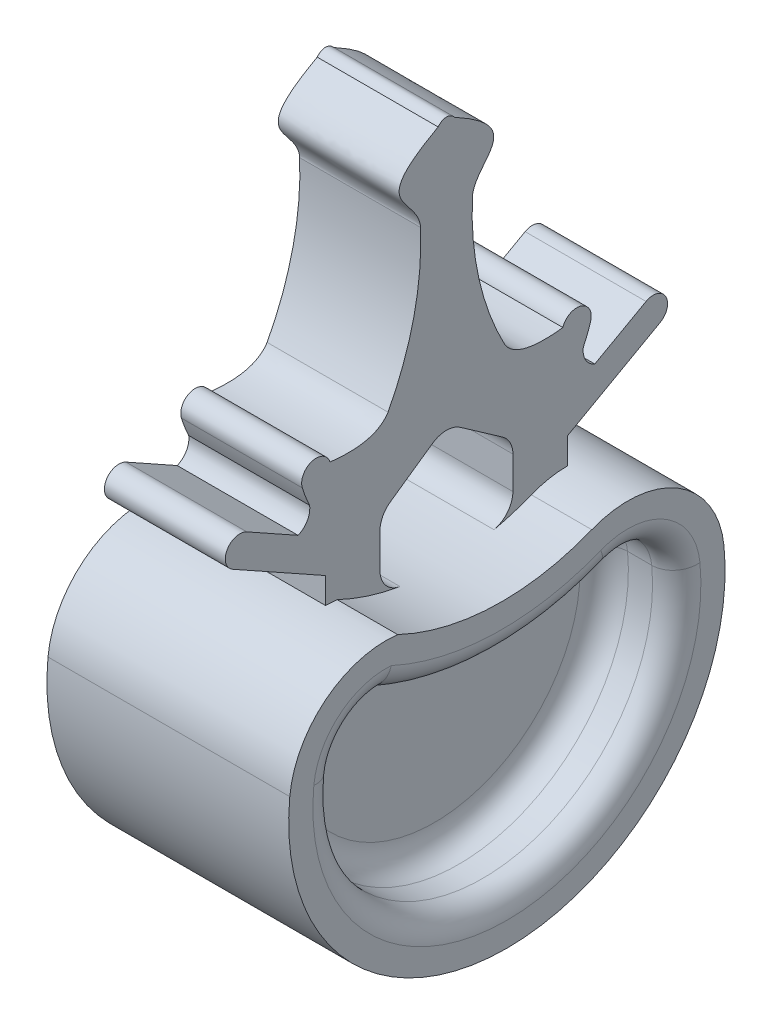
SolidWorks part; units mm, degrees
ref_plane "前视基准面" through (0, 0, 0) normal (0, 0, 1) x (1, 0, 0)
ref_plane "上视基准面" through (0, 0, 0) normal (0, 1, 0) x (1, 0, 0)
ref_plane "右视基准面" through (0, 0, 0) normal (1, 0, 0) x (0, 0, -1)
other "Configuration Table"
sketch "Sketch3" plane through (0, 0, 0) normal (1, 0, 0) x (0, 0, -1)
  line L0 (0, 0) -> (-5, 0) construction
  line L1 (0, 0) -> (5, 0) construction
  arc A0 (-5, 0) -> (5, 0) centre (0, -0.5) ccw construction
  arc A1 (-8.9801, 0.398) -> (8.9801, 0.398) centre (0, -0.5) ccw
  arc A4 (8.9801, 0.398) -> (3.5117, 3.7128) centre (5, 0) ccw
  arc A5 (-4.5181, 3.9709) -> (3.5117, 3.7128) centre (-0.209, 12.9948) ccw
  arc A6 (-4.5181, 3.9709) -> (-8.9801, 0.398) centre (-5, 0) ccw
  point P5 (0, -5.5249)
  point P8 (-0.5302, 3)
  dimension "D4" = 4
  dimension "D5" = 10
  dimension "D3" = 4
  dimension "D7" = 9.0249
  dimension "D1" = 5
  dimension "D2" = 5
  dimension "D6" = 3
  dimension "D8" = 0.5
extrude "Boss-Extrude2" add sketch "Sketch3" along normal blind 10
sketch "Sketch4" plane through (10, 0, 0) normal (1, 0, 0) x (0, 0, -1)
  arc A8 (-5.0165, 1.9999) -> (-6.9901, 0.199) centre (-5, 0) ccw
  arc A9 (-6.9901, 0.199) -> (6.9901, 0.199) centre (0, -0.5) ccw
  arc A10 (6.9901, 0.199) -> (4.2559, 1.8564) centre (5, 0) ccw
  arc A11 (-5.0165, 1.9999) -> (4.2559, 1.8564) centre (-0.209, 12.9948) ccw
  arc A12 (-5.0165, 1.9999) -> (-6.9901, 0.199) centre (-5, 0) ccw
  arc A13 (-6.9901, 0.199) -> (6.9901, 0.199) centre (0, -0.5) ccw
  arc A14 (6.9901, 0.199) -> (4.2559, 1.8564) centre (5, 0) ccw
  arc A15 (-5.0165, 1.9999) -> (4.2559, 1.8564) centre (-0.209, 12.9948) ccw
  dimension "D1" = 2
extrude "Cut-Extrude1" cut sketch "Sketch4" against normal blind 3
ref_plane "Plane1" through (5, 0, 0) normal (1, 0, 0) x (0, 0, -1)
sketch "Sketch5" plane through (5, 0, 0) normal (1, 0, 0) x (0, 0, -1)
  line L0 (0, 0) -> (0, 8) construction
  line L1 (0, 8) -> (2.7485, 6.0755)
  line L2 (2.7485, 6.0755) -> (2.7485, 3.3062)
  line L3 (0, 8) -> (0, 13) construction
  line L4 (0, 10.5) -> (4.9985, 7)
  line L5 (4.9985, 7) -> (4.9985, 4)
  line L6 (-4.9985, 7) -> (-4.9985, 4)
  line L7 (-2.7485, 6.0755) -> (-2.7485, 3.3062)
  line L8 (0, 8) -> (-2.7485, 6.0755)
  line L9 (0, 10.5) -> (-4.9985, 7)
  line L10 (0, 13) -> (0, 18) construction
  line L11 (1.3449, 9.5583) -> (0.5651, 18.4709)
  line L12 (-1.3449, 9.5583) -> (-0.5651, 18.4709)
  arc A0 (8.9801, 0.398) -> (3.5117, 3.7128) centre (5, 0) ccw construction
  arc A9 (-4.5181, 3.9709) -> (-8.9801, 0.398) centre (-5, 0) ccw
  arc A10 (-8.9801, 0.398) -> (8.9801, 0.398) centre (0, -0.5) ccw
  arc A11 (8.9801, 0.398) -> (3.5117, 3.7128) centre (5, 0) ccw
  arc A12 (-4.5181, 3.9709) -> (3.5117, 3.7128) centre (-0.209, 12.9948) ccw
  arc A13 (-4.5181, 3.9709) -> (-8.9801, 0.398) centre (-5, 0) ccw
  arc A14 (-8.9801, 0.398) -> (8.9801, 0.398) centre (0, -0.5) ccw
  arc A15 (8.9801, 0.398) -> (3.5117, 3.7128) centre (5, 0) ccw
  arc A16 (-4.5181, 3.9709) -> (3.5117, 3.7128) centre (-0.209, 12.9948) ccw
  ellipse E0 centre (0, 18) end of major axis (0, 19) minor radius 0.6
  dimension "D1" = 8
  dimension "D2" = 5
  dimension "D3" = 2.25
  dimension "D4" = 125
  dimension "D5" = 3
  dimension "D6" = 5
  dimension "D7" = 1.2
  dimension "D8" = 2
  dimension "D9" = 50
  dimension "D10" = 0
extrude "Boss-Extrude3" add sketch "Sketch5" along normal mid plane 5 contours A15 L5 L4 L9 L6 A13 L7 L8 L1 L2 | E0 L12 L9 L4 L11 | E0 L9 region at (5, 7.1385, 1.4448) region at (5, 13.2604, 0) region at (5, 18, 0)
sketch "Sketch7" plane through (5, 0, 0) normal (1, 0, 0) x (0, 0, -1)
  line L0 (0, 19) -> (0, 0) construction
  line L1 (2.7485, 6.0755) -> (4.9985, 7) construction
  line L2 (4.9985, 7) -> (3.8735, 6.5377) construction
  line L3 (4.1823, 5.3066) -> (8.5466, 7.7435) construction
  line L4 (3.8897, 5.8305) -> (8.2541, 8.2674)
  line L5 (4.4748, 4.7828) -> (8.8391, 7.2197)
  line L6 (5, 4) -> (5, 5.076)
  line L7 (-5, 4) -> (-5, 5.076)
  line L8 (-4.1823, 5.3066) -> (-8.5466, 7.7435) construction
  line L9 (-3.8897, 5.8305) -> (-8.2541, 8.2674)
  line L10 (-4.4748, 4.7828) -> (-8.8391, 7.2197)
  line L74 (-5, 4) -> (-4.9985, 7)
  line L75 (-4.9985, 7) -> (-1.3449, 9.5583)
  line L76 (-1.3449, 9.5583) -> (-0.5937, 18.1443)
  line L77 (-0.5937, 18.1443) -> (0.5937, 18.1443)
  line L78 (0.5937, 18.1443) -> (1.3449, 9.5583)
  line L79 (1.3449, 9.5583) -> (4.9985, 7)
  line L80 (4.9985, 7) -> (5, 4)
  line L81 (4.9985, 7) -> (5, 4)
  line L82 (-5, 4) -> (0, 0)
  line L83 (0, 0) -> (5, 4)
  line L84 (-5, 4) -> (5, 4)
  arc A0 (3.8735, 6.5377) -> (5.389, 8.8743) centre (0.5038, 10.383) ccw construction
  arc A1 (4.269, 6.0865) -> (5.9623, 8.6972) centre (0.5038, 10.383) ccw
  arc A2 (3.4781, 6.989) -> (4.8157, 9.0513) centre (0.5038, 10.383) ccw
  arc A3 (3.4781, 6.989) -> (4.269, 6.0865) centre (3.8735, 6.5377) ccw
  arc A4 (5.9623, 8.6972) -> (4.8157, 9.0513) centre (5.389, 8.8743) ccw
  arc A5 (1.0768, 15.6644) -> (2.4164, 9.6362) centre (12.6356, 15.07) ccw
  arc A6 (5.66, 7.9233) -> (6.1364, 7.0849) centre (6.4354, 7.8094) ccw
  arc A7 (3.8897, 5.8305) -> (4.4748, 4.7828) centre (4.1823, 5.3066) ccw
  arc A8 (8.8391, 7.2197) -> (8.2541, 8.2674) centre (8.5466, 7.7435) ccw
  arc A9 (8.9801, 0.398) -> (3.5117, 3.7128) centre (5, 0) ccw construction
  arc A10 (-3.8897, 5.8305) -> (-4.4748, 4.7828) centre (-4.1823, 5.3066) cw
  arc A11 (-8.8391, 7.2197) -> (-8.2541, 8.2674) centre (-8.5466, 7.7435) cw
  arc A12 (-5.66, 7.9233) -> (-6.1364, 7.0849) centre (-6.4354, 7.8094) cw
  arc A13 (-3.8735, 6.5377) -> (-5.389, 8.8743) centre (-0.5038, 10.383) cw construction
  arc A14 (-4.269, 6.0865) -> (-5.9623, 8.6972) centre (-0.5038, 10.383) cw
  arc A15 (-3.4781, 6.989) -> (-4.8157, 9.0513) centre (-0.5038, 10.383) cw
  arc A16 (-3.4781, 6.989) -> (-4.269, 6.0865) centre (-3.8735, 6.5377) cw
  arc A17 (-5.9623, 8.6972) -> (-4.8157, 9.0513) centre (-5.389, 8.8743) cw
  arc A18 (-1.0768, 15.6644) -> (-2.4164, 9.6362) centre (-12.6356, 15.07) cw
  ellipse E0 centre (0, 18) end of major axis (0, 19) minor radius 0.6 (0.5937, 18.1443) -> (-0.5937, 18.1443) ccw construction
  spline S0 degree 3 poles (0, 19) (3.4903, 17.2101) (1.2443, 16.8956) (1.0686, 15.6113) (1.073, 15.5843) knots 0 0 0 0 0.318084 0.324852 0.324852 0.324852 0.324852
  spline S1 degree 2 poles (2.4164, 9.6362) (2.9382, 8.8227) (4.8157, 9.0513) knots 0.827735 0.827735 0.827735 1 1 1
  spline S2 degree 2 poles (-2.4164, 9.6362) (-2.9382, 8.8227) (-4.8157, 9.0513) knots 0.827735 0.827735 0.827735 1 1 1
  spline S3 degree 3 poles (0, 19) (-3.4903, 17.2101) (-1.2443, 16.8956) (-1.0686, 15.6113) (-1.073, 15.5843) knots 0 0 0 0 0.318084 0.324852 0.324852 0.324852 0.324852
  point P17 (4.7934, 7.6008)
  point P28 (6.3644, 6.5251)
  point P49 (-6.3644, 6.5251)
  point P60 (-4.7934, 7.6008)
  point P78 (5.389, 8.8743)
  dimension "D1" = 0.6
  dimension "D2" = 0.6
  dimension "D3" = 0
extrude "Boss-Extrude4" add sketch "Sketch7" along normal mid plane 5 contours A17 A14 L74 L75 A15 | L74 A14 A12 L9 | A11 L10 L74 L9 | S0 S3 A18 S2 A15 L75 L76 L77 L78 L79 A2 S1 A5 | A1 A4 A2 L79 L80 | A6 A1 L81 L4 | L5 A8 L4 L80 region at (5, 6.8541, -6.9839) region at (5, 7.07, -5.4863) region at (5, 8.2716, -5.135) region at (5, 8.381, -4.3814) region at (5, 6.8541, 6.9839) region at (5, 7.07, 5.4863) region at (5, 8.2716, 5.135)
fillet "Fillet2" radius 1 5 edges at (5, 3.3227, 2.7485) (5, 3.4422, -2.7485) (5, 6.0755, -2.7485) (5, 8, 0) (5, 6.0755, 2.7485)
sketch "Sketch10" plane through (0, 0, 0) normal (-1, 0, 0) x (0, 0, 1)
  arc A8 (6.9901, 0.199) -> (5.0165, 1.9999) centre (5, 0) ccw
  arc A9 (-4.2559, 1.8564) -> (5.0165, 1.9999) centre (0.209, 12.9948) ccw
  arc A10 (-4.2559, 1.8564) -> (-6.9901, 0.199) centre (-5, 0) ccw
  arc A11 (-6.9901, 0.199) -> (6.9901, 0.199) centre (0, -0.5) ccw
  arc A12 (6.9901, 0.199) -> (5.0165, 1.9999) centre (5, 0) ccw
  arc A13 (-4.2559, 1.8564) -> (5.0165, 1.9999) centre (0.209, 12.9948) ccw
  arc A14 (-4.2559, 1.8564) -> (-6.9901, 0.199) centre (-5, 0) ccw
  arc A15 (-6.9901, 0.199) -> (6.9901, 0.199) centre (0, -0.5) ccw
  dimension "D1" = 2
extrude "Cut-Extrude2" cut sketch "Sketch10" against normal blind 3 contours A13 A12 A15 A14
fillet "Fillet1" radius 1 16 edges at (10, 1.4773, 6.3481) (10, -7.5249, 0) (10, 1.7103, -6.0367) (7, 1.4773, 6.3481) (7, -7.5249, 0) (7, 0.9963, 0.3948) (10, 0.9963, 0.3948) (7, 1.7103, -6.0367) (0, 0.9963, 0.3948) (0, 1.4773, 6.3481) (0, -7.5249, 0) (3, 1.4773, 6.3481) (3, -7.5249, 0) (3, 1.7103, -6.0367) (0, 1.7103, -6.0367) (3, 0.9963, 0.3948)
